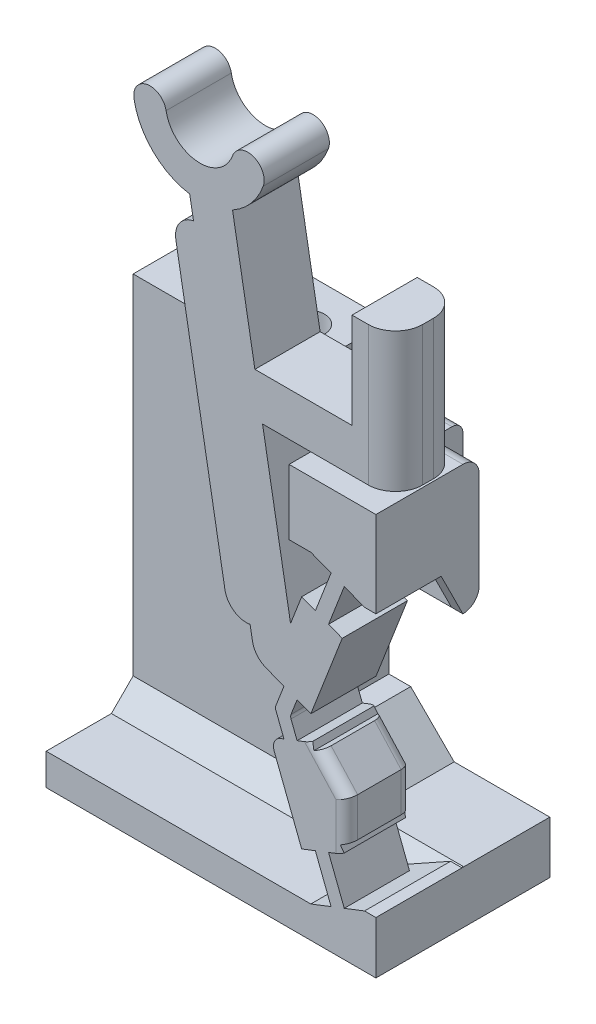
SolidWorks part; units mm, degrees
material "Nylon 6/12"
ref_plane "Front Plane" through (0, 0, 0) normal (0, 0, 1) x (1, 0, 0)
ref_plane "Top Plane" through (0, 0, 0) normal (0, 1, 0) x (1, 0, 0)
ref_plane "Right Plane" through (0, 0, 0) normal (1, 0, 0) x (0, 0, -1)
sketch "Sketch-SkeletonConfigUp" plane through (0, 0, 0) normal (0, 0, 1) x (1, 0, 0)
  line L0 (0, 0) -> (0, -50000) construction
  line L1 (-1.4217, 8.457) -> (-1.4217, 0) construction
  line L3 (0.7468, 14.0514) -> (-1.4217, 8.457) construction
  line L4 (-1.4217, 8.457) -> (0.7468, 2.8626) construction
  line L5 (0.7468, 14.0514) -> (2.1074, 19.3343) construction
  line L6 (-1.4217, 8.457) -> (-5.2203, 30) construction
  line L9 (0.7468, 14.0514) -> (0.7468, 2.8626) construction
  line L10 (0.7468, 2.8626) -> (0.7468, 0) construction
  line L11 (0, 0) -> (0.7468, 0) construction
  line L12 (0.7468, 0) -> (0, 0) construction
  dimension "D7" = 5.4552
  dimension "D10" = 6.745
  dimension "D3" = 2.1685
  dimension "D9" = 10
  dimension "D13" = 11.1888
  dimension "D14" = 30
  dimension "D5" = 10
  dimension "D2" = 21.8753
  dimension "D4" = 6
sketch "Sketch-SkeletonConfigDown" plane through (0, 0, 0) normal (0, 0, 1) x (1, 0, 0)
  line L0 (0, 0) -> (0, -50000) construction
  line L1 (0.7468, 14.0514) -> (0.7468, 2.8626) construction
  line L2 (5.9945, 14.5439) -> (0.7468, 14.0514) construction
  line L3 (0.7468, 14.0514) -> (2.9153, 8.457) construction
  line L4 (2.9153, 8.457) -> (0.7468, 2.8626) construction
  line L5 (0.7468, 14.0514) -> (-1.8086, 18.8711) construction
  line L6 (2.9153, 8.457) -> (-14.411, 21.8109) construction
  line L7 (0.7468, 2.8626) -> (5.9945, 14.5439) construction
  line L8 (-387.6937, -861.8102) -> (5.9945, 14.5439) construction
  line L10 (-1.4217, 8.457) -> (0.7468, 2.8626) construction
  line L11 (0.7468, 14.0514) -> (-1.4217, 8.457) construction
  line L12 (-1.4217, 8.457) -> (-5.2203, 30) construction
  line L13 (0.7468, 14.0514) -> (2.1074, 19.3343) construction
  dimension "D10" = 6.745
  dimension "D4" = 5.2707
  dimension "D5" = 119.553
  dimension "D2" = 52.378
  dimension "D3" = 31.19
ref_plane "Plane-Cam Base" through (3.8672, 0, 0) normal (1, 0, 0) x (0, 0, -1)
ref_plane "Plane-Down-to-Up Derailleur Clearance" through (1.3672, 0, 0) normal (1, 0, 0) x (0, 0, -1)
ref_plane "Plane-Cam Cavity Roof" through (-4.3828, 0, 0) normal (1, 0, 0) x (0, 0, -1)
sketch "Sketch-SwitchBossUp" plane through (0, 0, 0) normal (0, 0, 1) x (1, 0, 0)
  line L8 (-5.6979, 26.9497) -> (-5.5242, 25.9649)
  line L9 (-1.4217, 8.457) -> (-5.2203, 30) construction
  line L15 (-1.3633, 7.4072) -> (-0.7573, 7.6421) construction
  line L16 (-1.4217, 8.457) -> (0.7468, 2.8626) construction
  line L19 (0.0824, 13.2365) -> (0.6884, 13.0016) construction
  line L22 (0.8052, 15.1013) -> (1.4113, 14.8664) construction
  line L23 (-1.3633, 9.5069) -> (-1.9927, 9.7509)
  line L32 (1.0498, 2.9801) -> (0.4438, 2.7452) construction
  line L40 (-1.7703, 8.457) -> (-1.0732, 8.457) construction
  line L66 (-5.2203, 27.8193) -> (-5.2203, 50027.8193) construction
  line L74 (-4.078, 12.0039) -> (-6.3354, 24.8064)
  line L81 (2.3437, 2.4091) -> (2.8672, 2.4091)
  line L82 (-5.6111, 26.4573) -> (-3.6415, 26.8046) construction
  line L88 (-0.1116, 18.4627) -> (2.8672, 18.4627)
  line L92 (0.5949, 6.0212) -> (-1.2699, 5.2984) construction
  line L95 (-2.3469, 19.4627) -> (3.7672, 19.4627)
  line L96 (2.8672, 14.505) -> (2.8672, 18.4627)
  line L97 (3.7672, 19.4627) -> (3.7672, 25.8576)
  line L101 (-1.0603, 7.5246) -> (-1.4217, 8.457) construction
  line L103 (-5.2203, 30) -> (-3.0238, 29.2005) construction
  line L107 (-1.3633, 9.5069) -> (-0.7573, 9.272) construction
  line L109 (-5.2203, 30) -> (-7.5223, 29.5941) construction
  line L114 (-0.1279, 7.8861) -> (-0.7573, 7.6421)
  line L117 (2.8672, 0) -> (-0.1272, 0)
  line L121 (0.7468, 0) -> (0, 0) construction
  line L122 (0.8052, 1.8128) -> (-0.1272, 1.4513)
  line L123 (1.4113, 2.0477) -> (2.3437, 2.4091)
  line L125 (2.8672, 2.4091) -> (2.8672, 0)
  line L127 (-0.7573, 9.272) -> (-0.1279, 9.028)
  line L133 (0.4438, 14.1689) -> (1.0498, 13.934) construction
  line L134 (-0.1279, 9.028) -> (1.3178, 12.7576)
  line L135 (0.6884, 13.0016) -> (1.3178, 12.7576)
  line L142 (-0.1272, 1.4513) -> (-0.1272, 0)
  line L145 (1.04, 6.9167) -> (0.3056, 7.7216)
  line L151 (0.0824, 13.2365) -> (-0.547, 13.4805)
  line L152 (0.8052, 15.1013) -> (0.0824, 13.2365)
  line L153 (1.4113, 14.8664) -> (0.6884, 13.0016)
  line L169 (0.0824, 3.6776) -> (0.8052, 1.8128)
  line L170 (1.4113, 2.0477) -> (0.6884, 3.9125)
  line L177 (0.6884, 3.9125) -> (0.0824, 3.6776) construction
  line L184 (-0.547, 13.4805) -> (-1.0591, 12.1594)
  line L191 (-1.3633, 7.4072) -> (-1.9927, 7.1632)
  line L197 (3.7672, 25.8576) -> (1.7672, 25.8576)
  line L205 (1.7672, 25.8576) -> (1.7672, 21.4627)
  line L207 (12.0045, 16.6962) -> (12.0045, 16.6883) construction
  line L218 (0.6884, 3.9125) -> (1.3178, 4.1564)
  line L225 (-1.0591, 12.1594) -> (-2.3469, 19.4627)
  line L235 (-5.5242, 25.9649) -> (-2.7146, 10.0307) construction
  line L236 (-1.9927, 7.1632) -> (-0.547, 3.4336)
  line L237 (-2.7146, 10.0307) -> (-2.9195, 11.1927)
  line L241 (-1.4217, 8.457) -> (-1.0603, 9.3894) construction
  line L242 (1.7672, 21.4627) -> (-2.6996, 21.4627)
  line L243 (-0.7573, 7.6421) -> (-1.0381, 8.3667)
  line L244 (-1.0381, 8.5474) -> (-0.7573, 9.272)
  line L245 (-1.3633, 7.4072) -> (-1.7353, 8.3667)
  line L246 (-1.7353, 8.5474) -> (-1.3633, 9.5069)
  line L247 (-0.1279, 7.8861) -> (-0.0158, 7.597)
  line L248 (0.8052, 1.8128) -> (1.4113, 2.0477) construction
  line L249 (0.0824, 3.6776) -> (-0.547, 3.4336)
  line L250 (-1.9927, 9.7509) -> (-0.547, 13.4805) construction
  line L251 (0.7468, 14.0514) -> (-1.4217, 8.457) construction
  line L252 (-1.2699, 11.6157) -> (0.5949, 10.8928) construction
  line L253 (-2.3469, 19.4627) -> (-2.6996, 21.4627) construction
  line L254 (-1.9927, 9.7509) -> (-2.7146, 10.0307)
  line L255 (0.8052, 15.1013) -> (-0.1272, 15.4627)
  line L256 (1.4113, 14.8664) -> (2.3437, 14.505)
  line L257 (2.3437, 14.505) -> (2.8672, 14.505)
  line L258 (-2.6996, 21.4627) -> (-3.7283, 27.297)
  line L259 (3.8672, -55) -> (3.8672, 55) construction
  line L261 (1.5273, 6.3827) -> (1.5273, 4.5826)
  line L262 (1.5273, 4.5826) -> (1.2015, 4.4563)
  line L263 (0.5949, 6.0212) -> (1.5273, 6.3827) construction
  line L264 (1.2015, 4.4563) -> (0.5949, 6.0212) construction
  line L265 (1.2015, 4.4563) -> (1.3178, 4.1564)
  line L266 (0.5949, 6.0212) -> (-0.0158, 7.597) construction
  line L267 (-0.0158, 7.597) -> (0.5949, 6.0212) construction
  line L268 (0.5949, 6.0212) -> (1.2015, 4.4563) construction
  line L269 (-0.0158, 7.597) -> (0.5949, 6.0212) construction
  line L270 (0.5949, 6.0212) -> (1.2015, 4.4563) construction
  line L271 (1.5273, 6.3827) -> (1.04, 6.9167)
  line L272 (1.8311, 5.6598) -> (3.8672, 4.8706) construction
  line L273 (2.9153, 8.457) -> (0.7468, 2.8626) construction
  line L274 (-0.3375, 5.6598) -> (1.04, 6.9167) construction
  line L275 (-0.3375, 5.6598) -> (3.8672, 5.6598) construction
  line L276 (-0.1272, 15.4627) -> (-1.1272, 15.4627)
  line L277 (-1.1272, 15.4627) -> (-1.1272, 18.4627)
  line L278 (-1.1272, 18.4627) -> (-0.1116, 18.4627)
  line L279 (0.3056, 7.7216) -> (-0.0158, 7.597)
  arc A0 (-3.7283, 27.297) -> (-2.319, 28.944) centre (-5.2203, 30) ccw
  arc A1 (-5.6979, 26.9497) -> (-8.2609, 29.4639) centre (-5.2203, 30) cw
  arc A2 (-8.2609, 29.4639) -> (-6.7837, 29.7243) centre (-7.5223, 29.5941) cw
  arc A3 (-2.319, 28.944) -> (-3.7286, 29.457) centre (-3.0238, 29.2005) ccw
  arc A4 (-6.7837, 29.7243) -> (-3.7286, 29.457) centre (-5.2203, 30) ccw
  arc A19 (-6.3354, 24.8064) -> (-5.5242, 25.9649) centre (-5.3506, 24.98) cw
  circle A28 centre (-5.2203, 30) radius 2.3375 construction
  arc A30 (-4.078, 12.0039) -> (-2.9195, 11.1927) centre (-3.0932, 12.1775) ccw
  arc A31 (-1.0381, 8.3667) -> (-1.0381, 8.5474) centre (-0.805, 8.457) cw
  arc A32 (-1.7353, 8.3667) -> (-1.7353, 8.5474) centre (-1.5022, 8.457) cw
  point P5 (-4.6263, 26.6309)
  point P6 (-0.3375, 5.6598)
  point P45 (-0.3375, 11.2542)
  point P66 (4.5811, 6.2164)
  point P165 (0.7468, 14.0514)
  dimension "D23" = 1.5875
  dimension "D24" = 0.75
  dimension "D21" = 0.25
  dimension "D8" = 0.65
  dimension "D27" = 0.65
  dimension "D26" = 2
  dimension "D16" = 2
  dimension "D28" = 2
  dimension "D29" = 2
  dimension "D30" = 1
  dimension "D31" = 15
  dimension "D4" = 1.4169
  dimension "D6" = 0.65
  dimension "D7" = 2
  dimension "D11" = 1
  dimension "D12" = 90
  dimension "D13" = 60
  dimension "D14" = 2
  dimension "D15" = 1
  dimension "D17" = 2
  dimension "D19" = 0.1
  dimension "D22" = 42.38
  dimension "D18" = 3
  dimension "D25" = 1
  dimension "D32" = 1
  dimension "D20" = 1
  dimension "D33" = 1
extrude "Boss-Switch Body" add sketch "Sketch-SwitchBossUp" along normal blind 3
sketch "Sketch1" plane through (0, 0, 0) normal (0, 0, -1) x (-1, 0, 0)
  line L0 (-2.8672, 2.4091) -> (0.1272, 2.4091)
  line L1 (-2.8672, 0) -> (0.1272, 0)
  line L2 (-2.8672, 0) -> (-2.8672, 2.4091)
  line L4 (0.1272, 0) -> (0.1272, 2.4091)
  line L5 (1.1272, 14.505) -> (-2.8672, 14.505)
  line L10 (-2.8672, 14.505) -> (-2.8672, 18.4627)
  line L12 (-2.8672, 18.4627) -> (1.1272, 18.4627)
  line L14 (1.1272, 18.4627) -> (1.1272, 14.505)
  line L20 (-2.3437, 2.4091) -> (-2.8672, 2.4091) construction
  line L22 (-2.8672, 2.4091) -> (-2.3437, 2.4091) construction
  line L31 (0.1272, 0) -> (-2.8672, 0) construction
  line L32 (0.1272, 1.4513) -> (0.1272, 0) construction
extrude "Boss-Flange Width" add sketch "Sketch1" along normal blind 5
ref_plane "Plane-Sta2Sit Groove" through (-5.2203, 0, 0) normal (1, 0, 0) x (0, 0, -1)
ref_plane "Plane-Cam Outer Surface" through (-17.3003, 0, 0) normal (1, 0, 0) x (0, 0, -1)
ref_plane "Plane-FlangeTop" through (-12.3003, 0, 0) normal (1, 0, 0) x (0, 0, -1)
sketch "Sketch2" plane through (-12.3003, 0, 0) normal (1, 0, 0) x (0, 0, -1)
  line L0 (5, 18.4627) -> (-3, 18.4627) construction
  line L1 (5, 14.505) -> (1, 14.505)
  line L2 (5, 14.505) -> (5, 18.4627)
  line L3 (5, 18.4627) -> (1, 18.4627)
  line L4 (1, 14.505) -> (1, 18.4627)
  line L5 (5, 14.505) -> (-3, 14.505) construction
  line L11 (5, 1.4513) -> (-3, 1.4513)
  line L12 (5, 1.4513) -> (5, 0)
  line L13 (5, 0) -> (-3, 0)
  line L14 (-3, 1.4513) -> (-3, 0)
  line L15 (0, 8.457) -> (0, 30) construction
  line L16 (-3, 1.4513) -> (-3, 0) construction
  line L17 (5, 2.4091) -> (5, 0) construction
  line L19 (-3, 1.4513) -> (0, 1.4513) construction
  dimension "D1" = 1
extrude "Boss-Flange Height" add sketch "Sketch2" along normal up to surface (12.1731 mm away) up to face at (-0.1272, 1.2868, -0.6667)
sketch "Sketch17" plane through (0, 1.4513, 0) normal (0, -1, 0) x (1, 0, 0)
  line L0 (2.8672, -5) -> (-12.3003, -5)
  line L1 (2.8672, -5) -> (-12.3003, -5) construction
  line L2 (-12.3003, -5) -> (-12.3003, -1)
  line L3 (-12.3003, -1) -> (2.8672, -1)
  line L4 (2.8672, -1) -> (2.8672, -5)
  line L5 (-12.3003, -1) -> (-12.3003, -5) construction
  line L7 (-1.1272, -1) -> (-12.3003, -1) construction
extrude "Boss-Flange Support" add sketch "Sketch17" against normal up to surface (13.0536 mm away) up to face at (-1.4588, 14.505, -0.6)
sketch "Sketch27" plane through (0, 0, 0) normal (0, 0, 1) x (1, 0, 0)
  line L1 (-0.1272, 15.4627) -> (2.3437, 14.505)
  line L2 (2.3437, 14.505) -> (-1.1272, 14.505)
  line L3 (-1.1272, 14.505) -> (-1.1272, 15.4627)
  line L4 (-1.1272, 15.4627) -> (-0.1272, 15.4627)
  line L6 (-1.1272, 14.505) -> (2.8672, 14.505) construction
  line L7 (2.3437, 14.505) -> (1.2712, 14.505) construction
  line L8 (2.3437, 2.4091) -> (-0.1272, 2.4091)
  line L9 (-0.1272, 2.4091) -> (-0.1272, 1.4513)
  line L10 (-0.1272, 1.4513) -> (2.3437, 2.4091)
extrude "Cut-Wall Gap" cut sketch "Sketch27" against normal up to surface (1 mm away) up to face at (-2.6719, 9.207, -1)
ref_plane "Plane-Tap Depth" through (0, 13.4627, 0) normal (0, 1, 0) x (1, 0, 0)
sketch "Sketch-HolePositions" plane through (0, 0, 0) normal (0, -1, 0) x (1, 0, 0)
  line L0 (-12.3003, -3) -> (2.8672, -3) construction
  line L1 (2.8672, -5) -> (-12.3003, -5) construction
  line L2 (2.8672, -5) -> (2.8672, 3) construction
  line L4 (-12.3003, -22.2167) -> (-12.3003, 22.2167) construction
  point P6 (-10.3003, -3)
  point P7 (-6.3003, -3)
  dimension "D1" = 2
  dimension "D2" = 4
  dimension "D3" = 2
sketch "Sketch6" plane through (0, 0, 0) normal (0, -1, 0) x (-1, 0, 0)
  point P0 (10.3003, 3)
  point P3 (6.3003, 3)
hole_wizard "Tap Drill for M2x0.4 Tap1" positions "Sketch6" profile "Sketch5" hole size "M2x0.4" standard "ANSI Metric" end condition through all
sketch "Sketch5" plane through (-10.3003, 0, -3) normal (1, 0, 0) x (0, 0, -1)
  line L0 (0, 0) -> (0, 30.3441)
  line L1 (0, 30.3441) -> (0.8, 30.3441)
  line L2 (0.8, 30.3441) -> (0.8, 0)
  line L5 (0.8, 0) -> (0, 0)
  line L11 (0, -6.35) -> (0, 107.95) construction
  dimension "Thru Hole Dia." = 1.6
  dimension "Thru Hole Depth" = 30.3441
sketch "Sketch9" plane through (0, 0, 0) normal (0, -1, 0) x (1, 0, 0)
  point P0 (-10.3003, -3)
  point P3 (-6.3003, -3)
hole_wizard "M2 Clearance Hole2" positions "Sketch9" profile "Sketch8" hole size "M2" standard "ANSI Metric"
sketch "Sketch8" plane through (-10.3003, 0, -3) normal (1, 0, 0) x (0, 0, -1)
  line L0 (0, 0) -> (0, 14.1838)
  line L1 (0, 14.1838) -> (1.2, 13.4627)
  line L2 (1.2, 13.4627) -> (1.2, 0)
  line L5 (1.2, 0) -> (0, 0)
  line L10 (0, 14.1838) -> (-1.2, 13.4627) construction
  line L11 (0, -6.35) -> (0, 107.95) construction
  dimension "Hole Dia." = 2.4
  dimension "Hole Depth" = 13.4627
  dimension "Drill Angle" = 118
sketch "Sketch-Measurements for Derailleur Ramps" [suppressed] plane through (0, 0, 0) normal (0, 0, 1) x (1, 0, 0)
  line L0 (2.8784, 16.9852) -> (4.2265, 19.8331)
  line L1 (3.5524, 18.4092) -> (3.0492, 18.6474)
  line L2 (1.9779, 11.0613) -> (4.4465, 28.5428) construction
  line L3 (3.0492, 18.6474) -> (-4.0642, 13.8428)
  line L4 (7.1843, 11.0614) -> (-9.9544, 15.2993) construction
  line L5 (3.0492, 18.6474) -> (2.1536, 12.3053)
  line L6 (2.1536, 12.3053) -> (-4.0642, 13.8428)
  line L7 (-0.5075, 16.2451) -> (-0.5075, 18.6474)
  line L8 (-0.5075, 18.6474) -> (3.0492, 18.6474)
  line L9 (7.1843, 11.0614) -> (1.9779, 11.0613)
  line L10 (5.8827, 8.6389) -> (3.2795, 8.6389)
  line L12 (7.1843, 11.0614) -> (4.5811, 6.2164) construction
  line L13 (4.5811, 8.6389) -> (4.5811, 8.7912)
  line L14 (4.5811, 6.2164) -> (5.8827, 8.6389)
  line L15 (1.9779, 11.0613) -> (4.5811, 6.2164) construction
  line L16 (3.2795, 8.6389) -> (4.5811, 6.2164)
  line L17 (5.8827, 8.6389) -> (5.8827, 8.7912)
  dimension "D1" = 3.5567
  dimension "D2" = 1.3016
ref_plane "Plane1" [suppressed] through (0, 6.9404, 0) normal (0, 1, 0) x (1, 0, 0)
ref_plane "Plane-Cantilever Cut" [suppressed] through (7.0848, 8.5204, -1.9058) normal (-0.6301, -0.7578, 0.1695) x (-0.7765, 0.6151, -0.1368)
ref_plane "Plane-Symmetry Plane" through (0, 0, 1.5) normal (0, 0, 1) x (1, 0, 0)
sketch "Sketch-Cable Center Point" plane through (0, 0, 1.5) normal (0, 0, 1) x (1, 0, 0)
  line L0 (-5.2203, 30) -> (-5.0825, 29.2183)
  line L1 (-1.4217, 8.457) -> (-5.2203, 30) construction
  point P0 (-5.2203, 30)
  dimension "D1" = 0.7937
sketch "Sketch28" plane through (0, 0, -1) normal (0, 0, 1) x (1, 0, 0)
  line L0 (2.8672, 14.505) -> (2.8672, 2.4091)
  line L1 (2.3437, 2.4091) -> (2.8672, 2.4091) construction
  line L2 (2.8672, 14.505) -> (-3.5328, 14.505)
  line L3 (-3.5328, 14.505) -> (-3.5328, 2.4091)
  line L4 (-3.5328, 2.4091) -> (2.8672, 2.4091)
  line L5 (3.8672, -55) -> (3.8672, 55) construction
  line L6 (-7.5003, 13.4627) -> (-5.1003, 13.4627) construction
  line L7 (-7.5003, 13.4627) -> (-5.1003, 13.4627) construction
  dimension "D1" = 7.4
chamfer "Chamfer-Flange Support" [suppressed] distance 1.5 angle 45
chamfer "Chamfer-Flange Support 3" distance 1 angle 45 1 edges at (-6.2138, 1.4513, -1)
fillet "Fillet1" radius 1 1 edges at (-2.7146, 10.0307, 1.5)
fillet "Fillet2" radius 0.5 1 edges at (-1.9927, 7.1632, 1.5)
extrude "Cut-Print Support Clearance" cut sketch "Sketch28" against normal through all
sketch "Sketch12" plane through (0, 18.4627, 0) normal (0, 1, 0) x (1, 0, 0)
  line L3 (2.8672, 5) -> (2.8672, 2.75)
  line L4 (2.8672, -3) -> (2.8672, 5) construction
  line L5 (1.1172, 2.75) -> (-4.5328, 2.75)
  line L6 (-4.5328, 2.75) -> (-4.5328, 5)
  line L7 (-12.3003, 5) -> (2.8672, 5) construction
  line L8 (-4.5328, 5) -> (2.8672, 5)
  line L9 (3.8672, -55) -> (3.8672, 55) construction
  line L11 (1.1172, 2.75) -> (1.1172, 1.75)
  line L12 (1.1172, 1.75) -> (2.8672, 1.75)
  line L13 (2.8672, 1.75) -> (2.8672, 2.75)
  line L14 (2.8672, 2.75) -> (1.1172, 2.75) construction
  dimension "D1" = 8.4
  dimension "D2" = 2.25
  dimension "D3" = 1.75
  dimension "D4" = 1
extrude "Cut-Up-to-Down Derailleur Clearance" cut sketch "Sketch12" against normal blind 8
sketch "Sketch30" plane through (0, 25.8576, 0) normal (0, 1, 0) x (1, 0, 0)
  line L0 (1.9672, 0) -> (3.7672, -2.8)
  line L1 (3.7672, 0) -> (1.7672, 0) construction
  line L2 (3.7672, -3) -> (3.7672, 0) construction
  line L3 (3.7672, -2.8) -> (3.7672, 0)
  line L4 (3.7672, 0) -> (1.9672, 0)
  line L5 (1.7672, -3) -> (1.7672, 0) construction
  line L6 (3.7672, -3) -> (1.7672, -3) construction
  dimension "D1" = 0.2
  dimension "D2" = 0.2
extrude "Cut-Up-to-Down Cantilever Slope" [suppressed] cut sketch "Sketch30" against normal up to surface (4.3949 mm away)
fillet "Fillet3" radius 0.5 4 edges at (1.5273, 5.4827, 0) (1.5273, 5.4827, 3) (0.9165, 7.0521, 0) (0.9165, 7.0521, 3)
fillet "Fillet4" [suppressed] radius 0.5
fillet "Fillet5" radius 1.25 2 edges at (3.7672, 22.6602, 0) (3.7672, 22.6602, 3)
sketch "Sketch32" plane through (0, 14.505, 0) normal (0, -1, 0) x (1, 0, 0)
  line L0 (-3.5328, -2.75) -> (-3.5328, -1)
  line L1 (-3.5328, -1) -> (2.8672, -1)
  line L4 (2.8672, -1) -> (2.8672, -1.75)
  line L5 (2.8672, -1.75) -> (1.1172, -1.75)
  line L6 (1.1172, -1.75) -> (1.1172, -2.75)
  line L7 (1.1172, -2.75) -> (-3.5328, -2.75)
  line L8 (2.8672, 3) -> (2.8672, -5) construction
extrude "Boss-Extrude2" add sketch "Sketch32" along normal blind 2
fillet "Fillet7" radius 0.75 2 edges at (1.9922, 12.505, -1.75) (1.9922, 18.4627, -1.75)
sketch "Sketch34" plane through (0, 0, -5) normal (0, 0, -1) x (-1, 0, 0)
  line L0 (3.5328, 11.755) -> (4.5328, 11.755)
  line L1 (3.5328, 10.4627) -> (3.5328, 12.505) construction
  line L2 (4.5328, 10.4627) -> (4.5328, 18.4627) construction
  line L3 (4.5328, 11.755) -> (4.5328, 4.4091)
  line L4 (4.5328, 4.4091) -> (3.5328, 4.4091)
  line L5 (3.5328, 10.4627) -> (3.5328, 2.4091) construction
  line L6 (3.5328, 4.4091) -> (3.5328, 11.755)
  line L7 (3.5328, 2.4091) -> (-2.8672, 2.4091) construction
  line L8 (3.5328, 12.505) -> (-1.1172, 12.505) construction
  dimension "D1" = 2
  dimension "D2" = 0.75
extrude "Cut-Extrude1" cut sketch "Sketch34" against normal up to surface (4 mm away) up to face at (-2.2593, 12.6617, -1)
chamfer "Chamfer1" distance 2 angle 45 1 edges at (-3.5328, 2.4091, -3)
fillet "Fillet9" radius 0.5 2 edges at (-1.2078, 12.505, -2.75) (-1.7078, 18.4627, -2.75)
sketch "Sketch33" plane through (2.8672, 0, 0) normal (1, 0, 0) x (0, 0, -1)
  line L0 (1, 14.505) -> (0, 14.505)
  line L1 (-3, 14.505) -> (1, 14.505) construction
  line L2 (0, 14.505) -> (1, 12.505)
  line L3 (1, 12.505) -> (1, 14.505) construction
  line L4 (1, 12.505) -> (1, 14.505)
  arc A0 (1, 12.505) -> (1.75, 13.255) centre (1, 13.255) ccw construction
  dimension "D1" = 1
extrude "Boss-Support Chamfer" add sketch "Sketch33" against normal up to vertex (0.5235 mm away)
chamfer "Chamfer3" distance 0.75 angle 30 2 edges at (-3.5328, 12.6514, -2.6036) (-3.5328, 12.505, -1.625)
fillet "Fillet10" radius 0.5 1 edges at (-4.0328, 11.755, -2.75)
equation "\"axle-diameter\"=2"
equation "\"switch-thickness\"=12"
equation "\"base-width\"=4.0"
equation "\"axle-bushing-radius\"=3"
equation "\"clearance\"= 0.25"
equation "\"arm-width\"=1.5"
equation "\"min-diameter\"=70"
equation "\"alpha\"=143.6120"
equation "\"gamma\"=119.5526"
equation "\"delta\"=145.9637"
equation "\"epsilon\"=6.7452"
equation "\"l_AB\"=8.8212"
equation "\"l_AC\"=4.4914"
equation "\"l_BD\"=5.2707"
equation "\"l_CD\"=3.8848"
equation "\"l_CE\"=10.9181"
equation "\"l_DF\"=5.4552"
equation "\"l_OA\"=7.7221"
equation "\"D7@Sketch-SkeletonConfigUp\" = \"l_DF\""
equation "\"D_groove\"=3.175"
equation "\"D5@Sketch-SkeletonConfigDown\" = \"gamma\""
equation "\"D4@Sketch-SkeletonConfigDown\" = \"l_BD\""
equation "\"hinge_length\"=1.5"
equation "\"hinge_depth\"=0.25"
equation "\"D10@Sketch-SkeletonConfigUp\"=\"epsilon\""
equation "\"D10@Sketch-SkeletonConfigDown\"=\"epsilon\""
equation "\"EE_dx\"=8.9056"
equation "\"EE_dy\"=8.1898"
equation "\"r_groove\"=\"D_groove\"/2"
equation "\"t_wall\"=25.4/16"
equation "\"width_lower\"=\"D_groove\"+\"t_wall\""
equation "\"cable_to_bottom\"=30.6257"
equation "\"switch_EE-up_base_dy\"=24"
equation "\"switch_EE-down_base_dy\"=16"
equation "\"D_axle\"=25.4/8"
equation "\"D_up_to_down\"=23.5"
equation "\"D_down_to_up\"=22"
equation "\"t_cam_base\"=7.5"
equation "\"D23@Sketch-SwitchBossUp\"=\"D_groove\"/2"
equation "\"D1@Sketch-Cable Center Point\"=\"D_groove\"/4"
